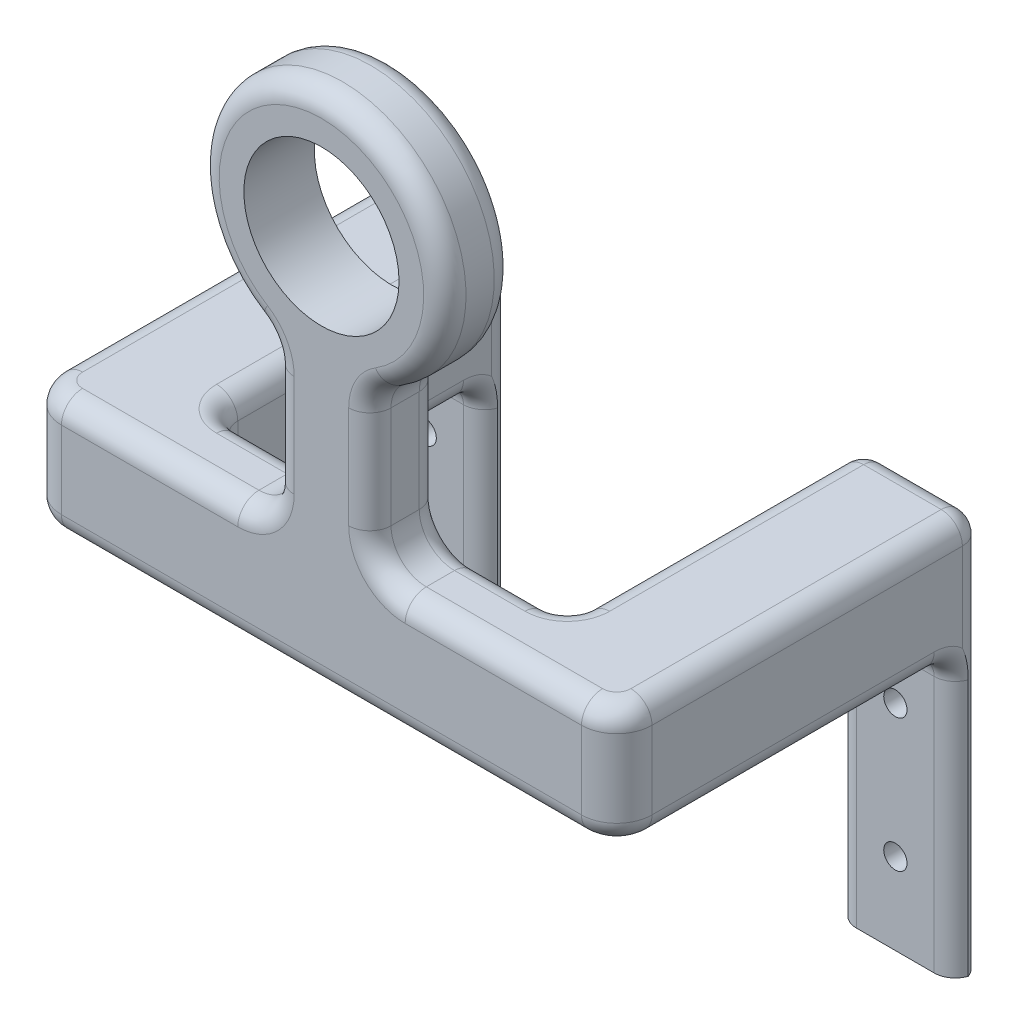
SolidWorks part; units mm, degrees
ref_plane "Front Plane" through (0, 0, 0) normal (0, 0, 1) x (1, 0, 0)
ref_plane "Top Plane" through (0, 0, 0) normal (0, 1, 0) x (1, 0, 0)
ref_plane "Right Plane" through (0, 0, 0) normal (1, 0, 0) x (0, 0, -1)
sketch "Croquis5" plane through (0, 0, 0) normal (0, 0, 1) x (1, 0, 0)
  circle A0 centre (0, 0) radius 11
  circle A1 centre (0, 0) radius 17.5
  dimension "D1" = 22
  dimension "D2" = 35
extrude "Saliente-Extruir4" add sketch "Croquis5" along normal blind 10
sketch "Croquis6" plane through (0, 0, 0) normal (0, 0, -1) x (-1, 0, 0)
  line L0 (0, 0) -> (0, 24.1849) construction
  line L1 (-6.8654, -16.0971) -> (-6.8654, -38.5919)
  line L10 (-6.8654, -38.5919) -> (-41.8654, -38.5919)
  line L15 (-41.8654, -38.5919) -> (-41.8654, -95)
  line L16 (-41.8654, -95) -> (-24.8654, -95)
  line L17 (-24.8654, -95) -> (-24.8654, -55.5919)
  line L18 (-24.8654, -55.5919) -> (24.8654, -55.5919)
  line L20 (24.8654, -38.5919) -> (24.8654, -95)
  line L21 (-41.8654, -38.5919) -> (-6.8654, -38.5919)
  line L22 (-41.8654, -38.5919) -> (-41.8654, -55.5919)
  line L23 (-41.8654, -55.5919) -> (41.8654, -55.5919)
  line L25 (-41.8654, -38.5919) -> (-24.8654, -38.5919)
  line L26 (-41.8654, -38.5919) -> (-41.8654, -95)
  line L27 (-41.8654, -95) -> (-24.8654, -95)
  line L28 (-24.8654, -38.5919) -> (-24.8654, -95)
  line L29 (41.8654, -95) -> (24.8654, -95)
  line L30 (41.8654, -38.5919) -> (41.8654, -95)
  line L31 (41.8654, -38.5919) -> (24.8654, -38.5919)
  line L32 (41.8654, -38.5919) -> (41.8654, -55.5919)
  line L33 (24.8654, -95) -> (24.8654, -55.5919)
  line L34 (41.8654, -95) -> (24.8654, -95)
  line L35 (41.8654, -38.5919) -> (41.8654, -95)
  line L36 (6.8654, -38.5919) -> (41.8654, -38.5919)
  line L37 (6.8654, -16.0971) -> (6.8654, -38.5919)
  line L38 (6.8654, -38.5919) -> (41.8654, -38.5919)
  circle A3 centre (0, 0) radius 17.5 construction
  arc A4 (6.8654, -16.0971) -> (-6.8654, -16.0971) centre (0, 0) cw
  circle A5 centre (-33.3654, -64.6222) radius 1.65
  circle A6 centre (-33.3654, -83.4648) radius 1.65
  circle A7 centre (33.3654, -64.6222) radius 1.65
  circle A8 centre (33.3654, -83.4648) radius 1.65
  point P31 (33.3654, -95)
  point P32 (-33.3654, -95)
  circle M30 centre (0, 0) radius 17.5
  dimension "D1" = 3.3
  dimension "D2" = 17
  dimension "D3" = 17
  dimension "D5" = 95
  dimension "D6" = 35
extrude "Saliente-Extruir5" add sketch "Croquis6" against normal blind 10 contours L37 L1 L10 L28 L18 L20 L36 M30 | L28 L21 L15 L23 | L30 L31 L20 L23 region at (0, -42.0931, 0) region at (33.3654, -47.0919, 0) region at (-33.3654, -47.0919, 0)
fillet "Redondeo2" radius 5 4 edges at (6.8654, -16.0971, 5) (-6.8654, -16.0971, 5) (6.8654, -38.5919, 5) (-6.8654, -38.5919, 5)
extrude "Saliente-Extruir6" add sketch "Croquis6<4>" along normal blind 38 contours L30 L31 L20 L23 | L28 L21 L15 L23 region at (33.3654, -47.0919, 0) region at (-33.3654, -47.0919, 0)
sketch "Croquis6<4>" plane through (0, 0, 0) normal (0, 0, -1) x (-1, 0, 0) same geometry as "Croquis6"
fillet "Redondeo3" radius 5 2 edges at (41.8654, -47.0919, 10) (-41.8654, -47.0919, 10)
extrude "Saliente-Extruir7" add sketch "Croquis6<5>" along normal blind 4 from surface contours L30 L23 L20 L29 | L23 L15 L16 L17 | L30 L31 L20 L23 | L28 L21 L15 L23 region at (33.3654, -47.0919, 0) region at (33.3654, -75.3288, 0) region at (-33.3654, -47.0919, 0) region at (-33.3654, -75.3288, 0) starting at face at (33.3654, -47.0919, -38)
sketch "Croquis6<5>" plane through (0, 0, 0) normal (0, 0, -1) x (-1, 0, 0) same geometry as "Croquis6"
fillet "Redondeo4" radius 3 11 edges at (41.8654, -75.2959, -38) (-41.8654, -75.2959, -38) (41.8654, -55.5919, -16.5) (40.4009, -55.5919, 8.5355) (-41.8654, -55.5919, -16.5) (-40.4009, -55.5919, 8.5355) (24.8654, -47.0919, 0) (-24.8654, -47.0919, 0) (0, -55.5919, 10) (33.3654, -55.5919, -38) (-33.3654, -55.5919, -38)
fillet "Redondeo5" radius 3 2 edges at (-33.3654, -38.5919, -42) (33.3654, -38.5919, -42)
fillet "Redondeo6" radius 3 9 edges at (24.8654, -76.7959, -38) (24.8654, -56.4706, -37.1213) (24.8654, -55.5919, -19) (23.9867, -55.5919, -0.8787) (0, -55.5919, 0) (-23.9867, -55.5919, -0.8787) (-24.8654, -55.5919, -19) (-24.8654, -56.4706, -37.1213) (-24.8654, -76.7959, -38)
fillet "Redondeo7" radius 3 34 edges at (-24.8654, -68.2959, -42) (-24.8654, -39.4706, -41.1213) (-24.8654, -38.5919, -21) (-23.9867, -38.5919, -0.8787) (-16.8654, -38.5919, 0) (-8.3299, -37.1274, 0) (-6.8654, -26.3545, 0) (-7.496, -16.6864, 0) (0, 17.5, 0) (7.496, -16.6864, 0) (24.8654, -68.2959, -42) (24.8654, -39.4706, -41.1213) (24.8654, -38.5919, -21) (23.9867, -38.5919, -0.8787) (16.8654, -38.5919, 0) (8.3299, -37.1274, 0) (-41.8654, -68.2959, -42) (-41.8654, -39.4706, -41.1213) (-41.8654, -38.5919, -17) (-40.4009, -38.5919, 8.5355) (-8.3299, -37.1274, 10) (-6.8654, -26.3545, 10) (-7.496, -16.6864, 10) (0, 17.5, 10) (7.496, -16.6864, 10) (6.8654, -26.3545, 10) (8.3299, -37.1274, 10) (41.8654, -68.2959, -42) (41.8654, -39.4706, -41.1213) (41.8654, -38.5919, -17) (40.4009, -38.5919, 8.5355) (6.8654, -26.3545, 0) (-24.3654, -38.5919, 10) (24.3654, -38.5919, 10)
